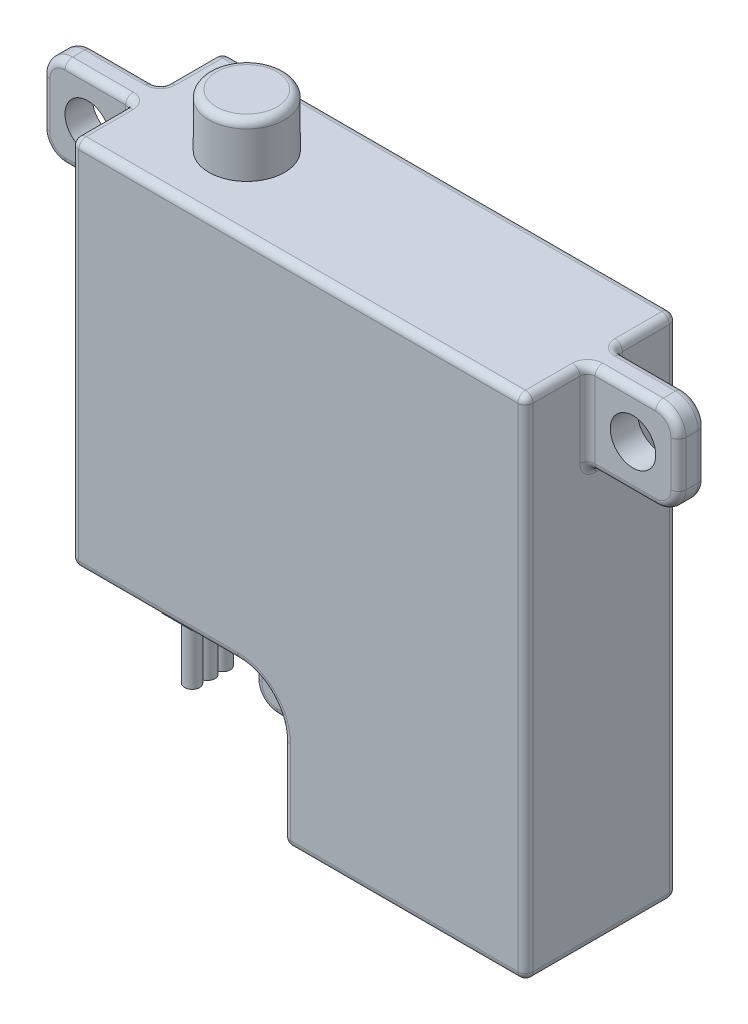
SolidWorks part; units mm, degrees
ref_plane "Front Plane" through (0, 0, 0) normal (0, 0, 1) x (1, 0, 0)
ref_plane "Top Plane" through (0, 0, 0) normal (0, 1, 0) x (1, 0, 0)
ref_plane "Right Plane" through (0, 0, 0) normal (1, 0, 0) x (0, 0, -1)
sketch "Sketch1" plane through (0, 0, 0) normal (0, 0, 1) x (1, 0, 0)
  line L0 (0, 0) -> (16, 0)
  line L1 (16, 0) -> (16, 33.5)
  line L2 (16, 33.5) -> (-14, 33.5)
  line L3 (-14, 33.5) -> (-14, 9)
  line L4 (-14, 9) -> (-3, 9)
  line L5 (0, 0) -> (0, 6)
  arc A0 (-3, 9) -> (0, 6) centre (-3, 6) cw
  dimension "D3" = 3
  dimension "D1" = 30
  dimension "D2" = 33.5
  dimension "D4" = 9
  dimension "D5" = 11
extrude "Boss-Extrude1" add sketch "Sketch1" along normal blind 10
sketch "Sketch2" plane through (-14, 0, 0) normal (-1, 0, 0) x (0, 0, 1)
  line L0 (5, 33.5) -> (5, 9) construction
  line L1 (10, 33.5) -> (0, 33.5) construction
  line L2 (10, 9) -> (0, 9) construction
  line L4 (4.1, 33.5) -> (5.9, 33.5)
  line L5 (4.1, 33.5) -> (4.1, 27.5)
  line L6 (4.1, 27.5) -> (5.9, 27.5)
  line L7 (5.9, 33.5) -> (5.9, 27.5)
  point P11 (5, 33.5)
  dimension "D1" = 1.8
  dimension "D2" = 6
extrude "Boss-Extrude2" add sketch "Sketch2" along normal blind 6
sketch "Sketch3" plane through (16, 0, 0) normal (1, 0, 0) x (0, 0, -1)
  line L0 (-5, 33.5) -> (-5, 0) construction
  line L1 (-10, 33.5) -> (0, 33.5) construction
  line L2 (-10, 0) -> (0, 0) construction
  line L4 (-5.9, 33.5) -> (-4.1, 33.5)
  line L5 (-5.9, 33.5) -> (-5.9, 27.5)
  line L6 (-5.9, 27.5) -> (-4.1, 27.5)
  line L7 (-4.1, 33.5) -> (-4.1, 27.5)
  point P10 (-5, 33.5)
  dimension "D1" = 1.8
  dimension "D2" = 6
extrude "Boss-Extrude3" add sketch "Sketch3" along normal blind 6
sketch "Sketch4" plane through (0, 0, 0) normal (-1, 0, 0) x (0, 0, 1)
  line L0 (5, 0) -> (5, 9) construction
  line L1 (10, 0) -> (0, 0) construction
  line L2 (10, 9) -> (0, 9) construction
  line L4 (4.1, 9) -> (5.9, 9)
  line L5 (4.1, 9) -> (4.1, 3)
  line L6 (4.1, 3) -> (5.9, 3)
  line L7 (5.9, 9) -> (5.9, 3)
  point P10 (5, 9)
  dimension "D1" = 1.8
  dimension "D2" = 6
extrude "Boss-Extrude4" add sketch "Sketch4" along normal blind 6
sketch "Sketch5" plane through (0, 0, 5.9) normal (0, 0, 1) x (1, 0, 0)
  line L0 (-20, 33.5) -> (-14, 33.5) construction
  line L1 (-20, 27.5) -> (-20, 33.5) construction
  line L2 (22, 33.5) -> (16, 33.5) construction
  line L3 (-20, 27.5) -> (-14, 27.5) construction
  line L5 (-6, 3) -> (-6, 9) construction
  line L6 (-6, 3) -> (0, 3) construction
  line L7 (22, 33.5) -> (22, 27.5) construction
  line L8 (22, 27.5) -> (16, 27.5) construction
  line L9 (20.5, 33.5) -> (22, 33.5)
  line L10 (22, 33.5) -> (22, 32)
  line L13 (20.5, 27.5) -> (22, 27.5)
  line L14 (22, 27.5) -> (22, 29)
  line L15 (-6, 4.5) -> (-6, 3)
  line L16 (-6, 3) -> (-4.5, 3)
  circle A0 centre (-17, 30.5) radius 1.5
  circle A1 centre (19, 30.5) radius 1.5
  circle A2 centre (-3, 6) radius 1.5
  arc A3 (-20, 32) -> (-18.5, 33.5) centre (-18.5, 32) cw
  arc A4 (-20, 29) -> (-18.5, 27.5) centre (-18.5, 29) ccw
  arc A5 (-6, 4.5) -> (-4.5, 3) centre (-4.5, 4.5) ccw
  arc A6 (20.5, 33.5) -> (22, 32) centre (20.5, 32) cw
  arc A7 (20.5, 27.5) -> (22, 29) centre (20.5, 29) ccw
  point P10 (-17, 33.5)
  point P14 (-20, 30.5)
  point P17 (19, 33.5)
  line M5 (-14, 33.5) -> (-20, 33.5)
  line M6 (-20, 33.5) -> (-20, 27.5)
  line M7 (-20, 27.5) -> (-14, 27.5)
  dimension "D1" = 3
  dimension "D2" = 1.5
  dimension "D4" = 24.5
  dimension "D5" = 14
extrude "Cut-Extrude2" cut sketch "Sketch5" against normal blind 6 contours A5 L15 L16 | A2 | A4 M6 M7 | A3 M6 M5 | A0 | A1 | L9 A6 L10 | A7 L13 L14 region at (21.6649, 33.1649, 5.9) region at (21.6649, 27.8351, 5.9) region at (-5.6649, 3.3351, 5.9) region at (-17, 30.5, 5.9) region at (19, 30.5, 5.9) region at (-3, 6, 5.9) region at (-19.6649, 33.1649, 5.9) region at (-19.6649, 27.8351, 5.9)
fillet "Fillet1" radius 0.5 63 edges at (-6, 9, 5) (0, 3, 5) (-16.25, 27.5, 5.9) (-19.5607, 27.9393, 5.9) (-20, 30.5, 5.9) (-19.5607, 33.0607, 5.9) (-16.25, 27.5, 4.1) (-19.5607, 27.9393, 4.1) (-20, 30.5, 4.1) (-19.5607, 33.0607, 4.1) (18.25, 27.5, 4.1) (21.5607, 27.9393, 4.1) (22, 30.5, 4.1) (21.5607, 33.0607, 4.1) (18.25, 27.5, 5.9) (21.5607, 27.9393, 5.9) (22, 30.5, 5.9) (21.5607, 33.0607, 5.9) (16, 27.5, 5) (16, 30.5, 4.1) (16, 30.5, 5.9) (-0.8787, 8.1213, 10) (-8.5, 9, 10) (16, 16.75, 10) (0, 3, 10) (-2.25, 3, 4.1) (0, 4.5, 4.1) (-0.8787, 8.1213, 4.1) (-4.5, 9, 4.1) (-6, 6.75, 4.1) (-5.5607, 3.4393, 4.1) (-3, 4.5, 4.1) (-6, 6.75, 5.9) (-4.5, 9, 5.9) (-0.8787, 8.1213, 5.9) (0, 4.5, 5.9) (-2.25, 3, 5.9) (-5.5607, 3.4393, 5.9) (-1.5, 6, 5.9) (-14, 27.5, 5) (-14, 30.5, 5.9) (-14, 21.25, 10) (-14, 9, 5) (-14, 30.5, 4.1) (0, 0, 5) (8, 0, 10) (16, 0, 5) (16, 33.5, 7.95) (1, 33.5, 10) (-14, 33.5, 7.95) (-16.25, 33.5, 5.9) (-16.25, 33.5, 4.1) (-14, 33.5, 2.05) (16, 33.5, 2.05) (18.25, 33.5, 4.1) (18.25, 33.5, 5.9) (8, 0, 0) (16, 16.75, 0) (1, 33.5, 0) (-14, 21.25, 0) (-8.5, 9, 0) (-0.8787, 8.1213, 0) (0, 3, 0)
sketch "Sketch6" plane through (0, 33.5, 0) normal (0, 1, 0) x (1, 0, 0)
  line L0 (-18.5, -5) -> (20.5, -5) construction
  line L1 (-18.5, -4.6) -> (-18.5, -5.4) construction
  line L2 (20.5, -4.6) -> (20.5, -5.4) construction
  line L3 (-14, -3.6) -> (-14, -0.5) construction
  circle A0 centre (-7.4, -5) radius 2.5
  dimension "D1" = 5
  dimension "D2" = 6.6
extrude "Boss-Extrude5" add sketch "Sketch6" along normal blind 3.5
fillet "Fillet2" radius 0.5 1 edges at (-9.9, 37, 5)
sketch "Sketch7" plane through (0, 9, 0) normal (0, -1, 0) x (1, 0, 0)
  line L1 (-11.5, 7.5) -> (-8.5, 7.5)
  line L2 (-11.5, 7.5) -> (-11.5, 2.5)
  line L3 (-11.5, 2.5) -> (-8.5, 2.5)
  line L4 (-8.5, 7.5) -> (-8.5, 2.5)
  line L5 (-13.5, 10) -> (-3, 10) construction
  line L6 (-14, 0.5) -> (-14, 9.5) construction
  dimension "D1" = 3
  dimension "D2" = 5
  dimension "D3" = 2.5
  dimension "D4" = 2.5
extrude "Boss-Extrude6" add sketch "Sketch7" along normal blind 0.75
sketch "Sketch9" plane through (0, 8.25, 0) normal (0, -1, 0) x (1, 0, 0)
  line L0 (-11.5, 7.5) -> (-11.5, 2.5) construction
  line L1 (-11, 3) -> (-9, 3)
  line L2 (-11, 3) -> (-11, 7)
  line L3 (-11, 7) -> (-9, 7)
  line L4 (-9, 3) -> (-9, 7)
  line L5 (-8.5, 7.5) -> (-11.5, 7.5) construction
  dimension "D1" = 2
  dimension "D2" = 4
  dimension "D3" = 0.5
  dimension "D4" = 0.5
extrude "Boss-Extrude7" add sketch "Sketch9" along normal blind 2
sketch "Sketch11" plane through (0, 6.25, 0) normal (0, -1, 0) x (1, 0, 0)
  line L0 (-11, 3) -> (-9, 3) construction
  line L1 (-11, 7) -> (-11, 3) construction
  circle A0 centre (-10, 6.01) radius 0.5
  circle A1 centre (-10, 5) radius 0.5
  circle A2 centre (-10, 3.99) radius 0.5
  dimension "D1" = 1
  dimension "D2" = 1
  dimension "D3" = 1
  dimension "D4" = 2
  dimension "D5" = 1.01
  dimension "D6" = 1.01
  dimension "D7" = 1
extrude "Boss-Extrude8" add sketch "Sketch11" along normal blind 4
